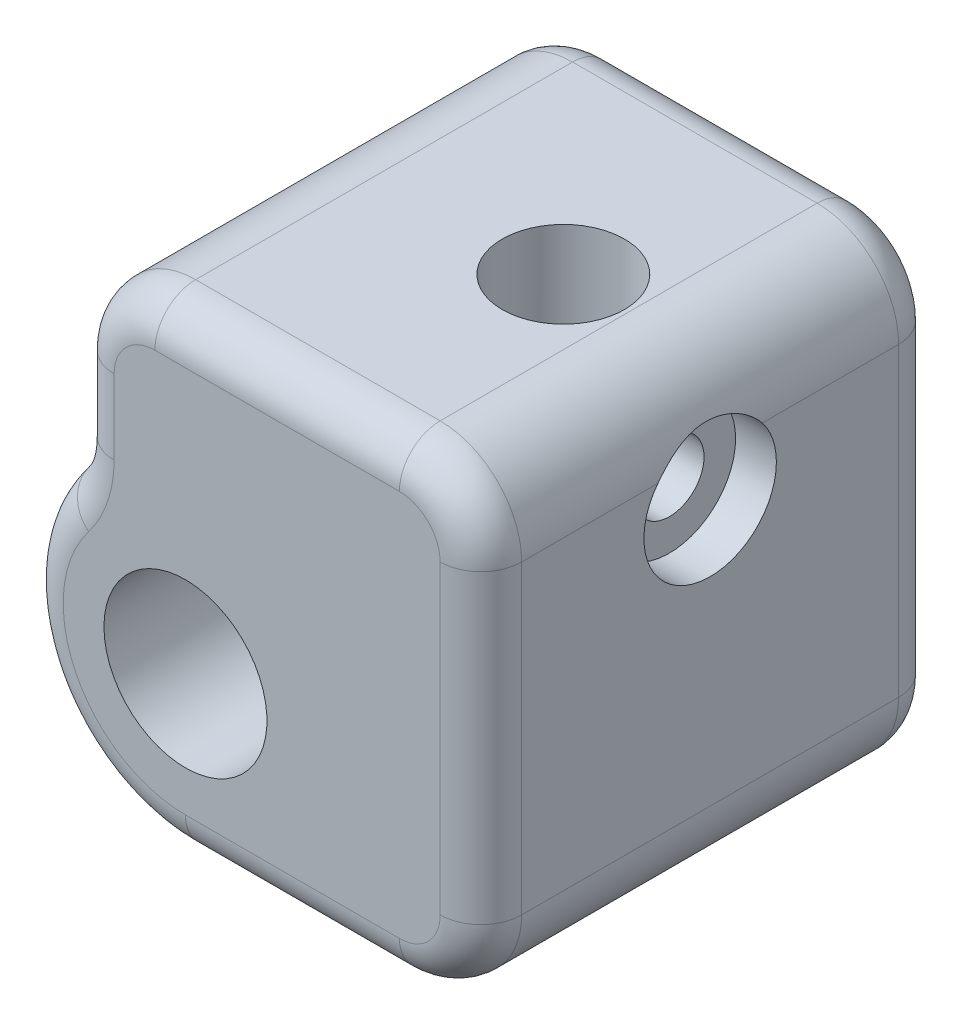
SolidWorks part; units mm, degrees
material "ABS"
ref_plane "Front" through (0, 0, 0) normal (0, 0, 1) x (1, 0, 0)
ref_plane "Top" through (0, 0, 0) normal (0, 1, 0) x (1, 0, 0)
ref_plane "Right" through (0, 0, 0) normal (1, 0, 0) x (0, 0, -1)
sketch "Esquisse1" plane through (0, 0, 0) normal (0, 0, 1) x (1, 0, 0)
  line L1 (-12.7953, 23) -> (7.2047, 23)
  line L2 (-12.7953, 23) -> (-12.7953, 13.8095)
  line L3 (-7.2953, 0) -> (7.2047, 0)
  line L4 (7.2047, 23) -> (7.2047, 0)
  circle A3 centre (-7.2953, 8) radius 4
  arc A4 (-12.7953, 13.8095) -> (-7.2953, 0) centre (-7.2953, 8) ccw
  dimension "D1" = 14.5
  dimension "D6" = 8
  dimension "D7" = 16
  dimension "D8" = 4
  dimension "D2" = 20
  dimension "D3" = 23
extrude "Boss.-Extru.1" add sketch "Esquisse1" along normal mid plane 22.5
sketch "Esquisse2" plane through (0, 0, 0) normal (0, 1, 0) x (1, 0, 0)
  circle A0 centre (0, 0) radius 3
  dimension "D1" = 6
extrude "Enlèv. mat.-Extru.1" cut sketch "Esquisse2" along normal through all from offset 4
hole_wizard "Chambrage pour vis à tête cylindrique à 6 pans creux (ou vis CHC) M31" positions "Esquisse8" profile "Esquisse9" counterbore size "M3" standard "Ansi Metric" end condition through all
sketch "Esquisse8" plane through (7.2047, 0, 0) normal (1, 0, 0) x (0, 0, -1)
  line L0 (-11.25, 17) -> (11.25, 17) construction
  line L1 (-11.25, 0) -> (-11.25, 23) construction
  line L2 (11.25, 0) -> (11.25, 23) construction
  line L3 (-11.25, 23) -> (11.25, 23) construction
  point P9 (0, 17)
  dimension "D1" = 6
sketch "Esquisse9" plane through (7.2047, 17, 0) normal (0, 1, 0) x (0, 0, -1)
  line L0 (0, 0) -> (0, 22.5)
  line L1 (0, 22.5) -> (1.7, 22.5)
  line L3 (1.7, 22.5) -> (1.7, 2)
  line L4 (1.7, 2) -> (3.25, 2)
  line L5 (3.25, 2) -> (3.25, 0)
  line L7 (3.25, 0) -> (0, 0)
  line L11 (0, -6.35) -> (0, 107.95) construction
  dimension "Diamètre du perçage jusqu'au prochain" = 3.4
  dimension "Profondeur du perçage jusqu'au prochain" = 22.5
  dimension "Diamètre du chambrage" = 6.5
  dimension "Profondeur du chambrage" = 2
sketch "Esquisse10" plane through (-12.7953, 0, 0) normal (-1, 0, 0) x (0, 0, 1)
  line L1 (1.5877, 14.25) -> (3.1754, 17)
  line L2 (3.1754, 17) -> (1.5877, 19.75)
  line L3 (1.5877, 19.75) -> (-1.5877, 19.75)
  line L4 (-1.5877, 19.75) -> (-3.1754, 17)
  line L5 (-3.1754, 17) -> (-1.5877, 14.25)
  line L6 (-1.5877, 14.25) -> (1.5877, 14.25)
  circle A0 centre (0, 17) radius 2.75 construction
  dimension "D1" = 5.5
extrude "Enlèv. mat.-Extru.6" cut sketch "Esquisse10" against normal blind 2.5
fillet "Congé3" radius 4 4 edges at (7.2047, 0, 0) (-12.7953, 13.8095, 0) (-12.7953, 23, 0) (7.2047, 23, 0)
fillet "Congé4" radius 2 18 edges at (-2.7953, 23, -11.25) (-11.6237, 21.8284, -11.25) (-12.7953, 17.1657, -11.25) (-13.0093, 14.0404, -11.25) (-14.4751, 4.4716, -11.25) (-2.0453, 0, -11.25) (6.0332, 1.1716, -11.25) (-2.7953, 23, 11.25) (-11.6237, 21.8284, 11.25) (-12.7953, 17.1657, 11.25) (-13.0093, 14.0404, 11.25) (-14.4751, 4.4716, 11.25) (-2.0453, 0, 11.25) (6.0332, 1.1716, 11.25) (7.2047, 11.5, -11.25) (7.2047, 11.5, 11.25) (6.0332, 21.8284, -11.25) (6.0332, 21.8284, 11.25)
